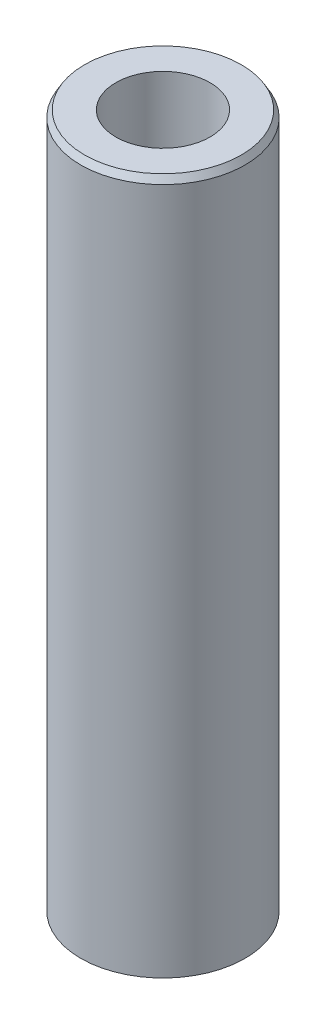
SolidWorks part; units mm, degrees
ref_plane "Front Plane" through (0, 0, 0) normal (0, 0, 1) x (1, 0, 0)
ref_plane "Top Plane" through (0, 0, 0) normal (0, 1, 0) x (1, 0, 0)
ref_plane "Right Plane" through (0, 0, 0) normal (1, 0, 0) x (0, 0, -1)
sketch "Sketch1" plane through (0, 0, 0) normal (0, 1, 0) x (1, 0, 0)
  circle A0 centre (0, 0) radius 57.5
  dimension "SHAFT_OD" = 115
extrude "Boss-Extrude1" add sketch "Sketch1" along normal blind 488.0983
sketch "Sketch2" plane through (0, 0, 0) normal (0, 1, 0) x (1, 0, 0)
  circle A0 centre (0, 0) radius 32.9705
  dimension "BORE_D" = 65.9409
extrude "Cut-Extrude1" cut sketch "Sketch2" along normal through all
chamfer "Chamfer1" distance 4.6813 angle 30 2 edges at (0, 488.0983, 57.5) (0, 0, 57.5) first distance on face at (0, 488.0983, 57.5) first distance on face at (0, 0, 32.9705)
